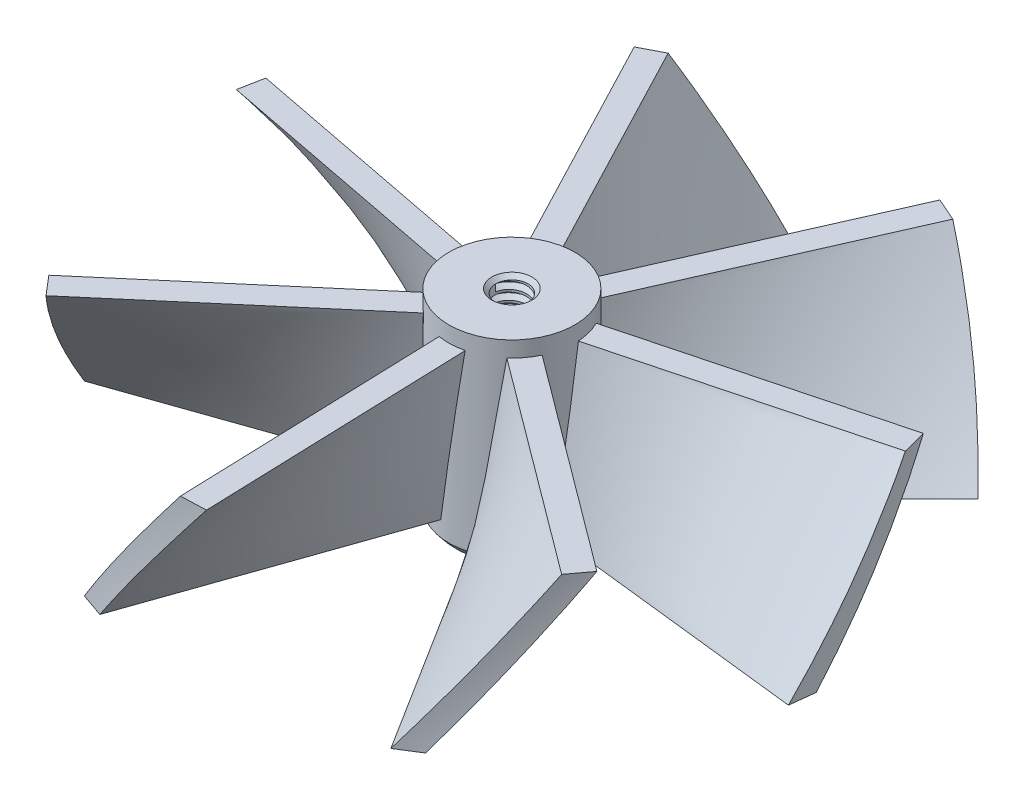
SolidWorks part; units mm, degrees
ref_plane "前视基准面" through (0, 0, 0) normal (0, 0, 1) x (1, 0, 0)
ref_plane "上视基准面" through (0, 0, 0) normal (0, 1, 0) x (1, 0, 0)
ref_plane "右视基准面" through (0, 0, 0) normal (1, 0, 0) x (0, 0, -1)
sketch "草图1" plane through (0, 0, 0) normal (0, 1, 0) x (1, 0, 0)
  circle A0 centre (0, 0) radius 4
  dimension "D1" = 8
extrude "凸台-拉伸1" add sketch "草图1" along normal blind 12
sketch "草图2" [suppressed] plane through (0, 0, 0) normal (0, 1, 0) x (1, 0, 0)
  circle A0 centre (0, 0) radius 2.1
  dimension "支撑柱直径" = 4.2
extrude "切除-拉伸2" [suppressed] cut sketch "草图2" along normal blind 6
fillet "圆角1" [suppressed] radius 2.1
ref_plane "基准面1" [suppressed] through (0, 1, 0) normal (0, 1, 0) x (1, 0, 0)
sketch "草图4" [suppressed] plane through (0, 1, 0) normal (0, 1, 0) x (1, 0, 0)
  circle A0 centre (0, 0) radius 4 construction
  circle A1 centre (0, 0) radius 4
curve "螺旋线/涡状线1" [suppressed] pitch 40 height 10 turns 0.25
ref_plane "基准面4" [suppressed] through (-4, 1, 0) normal (0, 0, 1) x (1, 0, 0)
sketch "草图7" [suppressed] plane through (-4, 1, 0) normal (0, 0, 1) x (1, 0, 0)
  line L0 (0, 11) -> (0, -1) construction
  line L1 (0, -0.5) -> (-12, -0.5)
  line L2 (0, -0.5) -> (0, 0.5)
  line L3 (0, 0.5) -> (-12, 0.5)
  line L4 (-12, -0.5) -> (-12, 0.5)
  spline S1 degree 3 poles (1965.7335, 349.2893) (250.7404, -87.9319) (-15.2554, -40.9347) (1.098, 5) (18.6688, 37.9953) (95.7941, 71.1214) (-1993.8368, -67.6679) knots -13.033984 -13.033984 -13.033984 -13.033984 0.25 0.5 0.75 10.15115 10.15115 10.15115 10.15115 only from (0, 0) to (4, 10) construction
  spline S2 degree 3 poles (0, 0) (0, 0.8318) (0.2082, 2.5006) (1.098, 5) (2.429, 7.4994) (3.4773, 9.1682) (4, 10) knots 0 0 0 0 0.25 0.5 0.75 1 1 1 1 construction
  dimension "D1" = 12
  dimension "D2" = 1
sweep "扫描2" [suppressed] add profiles "草图7" path "螺旋线/涡状线1"
fillet "圆角2" [suppressed] radius 4
fillet "圆角3" [suppressed] radius 4
pattern_circular "阵列(圆周)1" [suppressed] count 3 over 360 of bodies 110
sketch "草图8" plane through (0, 12, 0) normal (0, 1, 0) x (1, 0, 0)
  circle A0 centre (0, 0) radius 1.15
  dimension "D1" = 2.3
extrude "切除-拉伸3" [suppressed] cut sketch "草图8" against normal blind 5
sketch "草图17" plane through (0, 12, 0) normal (0, 1, 0) x (1, 0, 0)
  point P0 (0, 0)
hole_wizard "M2.5 螺纹孔1" positions "3D草图10" profile "草图28" tap size "M2.5" standard "GB"
sketch3d "3D草图10"
  point P0 (0, 12, 0)
sketch "草图28" plane through (0, 12, 0) normal (1, 0, 0) x (0, 0, 1)
  line L0 (0, 0) -> (0, 5.6159)
  line L1 (0, 5.6159) -> (1.025, 5)
  line L2 (1.025, 5) -> (1.025, 0.25)
  line L3 (1.025, 0.25) -> (1.275, 0)
  line L5 (1.275, 0) -> (0, 0)
  line L6 (-1.025, 0.25) -> (-1.275, 0) construction
  line L10 (0, 5.6159) -> (-1.025, 5) construction
  line L11 (0, -6.35) -> (0, 107.95) construction
  dimension "螺纹孔钻头直径" = 2.05
  dimension "螺纹孔钻头深度" = 5
  dimension "近端锥形沉头孔直径" = 2.55
  dimension "近端锥形沉头孔角度" = 90
  dimension "导头角度" = 118
cosmetic thread "孔螺蚊线2" parameters "D1"=5, "D2"=2.5
thread "螺纹线1" pitch 0.6 method cut profile "螺纹线轮廓2" start angle 0, offset 0, length 5, pitch 0.6, diameter 2.05
ref_plane "基准面11" through (-1.025, 11.75, 0) normal (0, 0, 1) x (-1, 0, 0)
sketch "螺纹线轮廓2" plane through (-1.025, 11.75, 0) normal (0, 0, 1) x (-1, 0, 0)
  line L0 (0, 0) -> (0, 0.6) construction
  line L1 (0, 0) -> (0.3248, 0.1875)
  line L2 (0.3248, 0.1875) -> (0.3248, 0.2625)
  line L3 (0.3248, 0.2625) -> (0, 0.45)
  line L4 (0.3248, 0.225) -> (0, 0.225) construction
  line L11 (0, 0) -> (0, 0.45)
  point P2 (0, 0)
  dimension "Pitch" = 0.6
  dimension "Profile_Angle" = 60
  dimension "Profile_Land" = 0.075
  dimension "Profile_Height" = 0.3248
ref_plane "基准面5" [suppressed] through (0, 1, 0) normal (0, -1, 0) x (-1, 0, 0)
sketch "草图10" [suppressed] plane through (0, 1, 0) normal (0, -1, 0) x (-1, 0, 0)
  circle A0 centre (0, 0) radius 4 construction
  circle A1 centre (0, 0) radius 4
curve "螺旋线/涡状线2" [suppressed] pitch 80 height 10 turns 0.125
ref_plane "基准面6" [suppressed] through (2.8284, 1, -2.8284) normal (-0.7071, 0, -0.7071) x (-0.7071, 0, 0.7071)
sketch "草图12" [suppressed] plane through (2.8284, 1, -2.8284) normal (-0.7071, 0, -0.7071) x (-0.7071, 0, 0.7071)
  line L0 (-0.4, 0) -> (8.4, 0) construction
  line L1 (-12, 0.6) -> (0, 0.6)
  line L2 (0, 0.6) -> (0, -0.6)
  line L3 (0, -0.6) -> (-12, -0.6)
  line L4 (-12, -0.6) -> (-12, 0.6)
  spline S0 degree 3 poles (0, 0) (0, 1.1108) (0.0919, 3.3335) (0.4961, 6.6665) (0.9248, 8.8892) (1.1716, 10) knots 0 0 0 0 0.333333 0.666667 1 1 1 1 construction
  point P0 (0, 0)
  dimension "D1" = 1.2
  dimension "D2" = 12
sweep "扫描3" [suppressed] add profiles "草图12" path "螺旋线/涡状线2"
pattern_circular "阵列(圆周)2" [suppressed] count 6 over 360 of bodies 113
ref_plane "基准面7" through (0, 1, 0) normal (0, -1, 0) x (-1, 0, 0)
sketch "草图13" plane through (0, 1, 0) normal (0, -1, 0) x (-1, 0, 0)
  circle A0 centre (0, 0) radius 4 construction
  circle A1 centre (0, 0) radius 4
curve "螺旋线/涡状线3" pitch 170 height 10 radius 4 centre (0, 1, 0) axis (0, 1, 0) start towards (0.7071, 0, -0.7071)
ref_plane "基准面9" through (0, 1, 0) normal (0, -1, 0) x (-1, 0, 0)
sketch "草图15" plane through (0, 1, 0) normal (0, -1, 0) x (-1, 0, 0)
  line L0 (-2.2627, 3.3941) -> (-3.3941, 2.2627) construction
  line L1 (-2.2117, 3.3431) -> (-14.2325, 15.3639)
  line L2 (-14.2325, 15.3639) -> (-15.3639, 14.2325)
  line L3 (-15.3639, 14.2325) -> (-3.3431, 2.2117)
  line L4 (-3.3431, 2.2117) -> (-2.2117, 3.3431)
  circle A0 centre (0, 0) radius 4 construction
  circle A1 centre (0, 0) radius 4 construction
  spline S0 degree 3 poles (1735.8868, 984.7252) (53.2042, -131.1038) (-18.2965, -7.6818) (13.7725, 14.2859) (103.0309, -96.9713) (-1545.2969, -1262.9378) knots -38.865078 -38.865078 -38.865078 -38.865078 0.333333 0.666667 39.865026 39.865026 39.865026 39.865026 only from (-2.8284, 2.8284) to (-1.6157, 3.6592) construction
  spline S1 degree 3 poles (-2.8284, 2.8284) (-2.7123, 2.9446) (-2.4656, 3.1626) (-2.0583, 3.4416) (-1.766, 3.5928) (-1.6157, 3.6592) knots 0 0 0 0 0.333333 0.666667 1 1 1 1 construction
  dimension "D1" = 1.6
  dimension "D2" = 17
sweep "扫描7" add profiles "草图15" path "螺旋线/涡状线3"
pattern_circular "阵列(圆周)3" count 7 over 360 about axis through (0, 12, 0) along (0, 1, 0) of "扫描7"
sketch "草图30" plane through (0, 0, 0) normal (0, 0, 1) x (1, 0, 0)
  line L0 (0, 0) -> (0, -2)
  line L1 (0, 0) -> (-4, 0)
  line L2 (-4, 0) -> (4, 0) construction
  line L3 (-4, 0) -> (-2.7313, -1.7964) construction
  line L4 (-2.7313, -1.7964) -> (0, -2) construction
  spline S1 degree 2 poles (-4, 0) (-2.7313, -1.7964) (0, -2) knots 0 0 0 1 1 1
  dimension "D1" = 2
revolve "旋转2" add sketch "草图30" angle 360 about L0
equation "\"D1@圆角1\"=\"支撑柱直径\"/2"
equation "\"扇叶长度\"= 17mm"
equation "\"D2@草图15\"=\"扇叶长度\""
